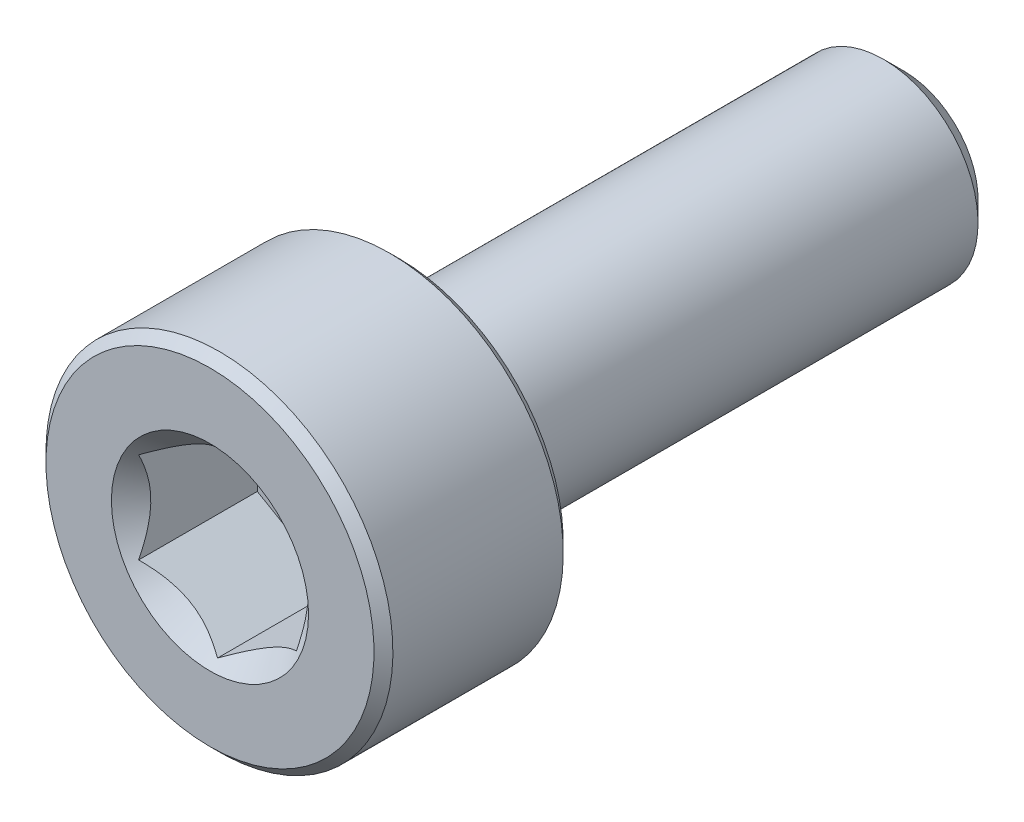
SolidWorks part; units mm, degrees
ref_plane "Front Plane" through (0, 0, 0) normal (0, 0, 1) x (1, 0, 0)
ref_plane "Top Plane" through (0, 0, 0) normal (0, 1, 0) x (1, 0, 0)
ref_plane "Right Plane" through (0, 0, 0) normal (1, 0, 0) x (0, 0, -1)
sketch "Sketch1" plane through (0, 0, 0) normal (1, 0, 0) x (0, 0, -1)
  line L0 (-5.5, 0) -> (5.5, 0) construction
  line L1 (5.5, 0) -> (5.5, 1.1752) construction
  line L2 (5.5, 1.1752) -> (5.1752, 1.5) construction
  line L3 (5.1752, 1.5) -> (5.125, 1.5) construction
  line L4 (5.125, 1.5) -> (-2.5, 1.5) construction
  line L5 (-2.5, 1.5) -> (-2.5, 2.75) construction
  line L6 (-2.5, 2.75) -> (-5.5, 2.75) construction
  line L7 (-5.5, 2.75) -> (-5.5, 0) construction
  line L8 (5.5, 1.1752) -> (5.5, 1.5) construction
  line L9 (5.4688, 1.5541) -> (5.7188, 1.1211) construction
  line L10 (5.7188, 1.1211) -> (5.9688, 1.5541) construction
  line L11 (5.9688, 1.5541) -> (5.4688, 1.5541) construction
  line L12 (5.7188, 1.5541) -> (5.7188, 1.5) construction
  line L13 (5.7188, 1.1211) -> (5.7188, 1.1752) construction
  line L14 (5.6875, 1.1752) -> (5.75, 1.1752) construction
  line L15 (5.5, 1.5) -> (5.9375, 1.5) construction
  line L16 (5.4844, 1.5271) -> (5.9531, 1.5271) construction
  line L17 (5.5, 0) -> (5.5, -1.5) construction
  line L18 (-2.65, 2.75) -> (-2.5, 2.6) construction
  line L19 (-5.35, 2.75) -> (-5.5, 2.6) construction
  line L20 (-2.5, 1.5) -> (-2.5, 0) construction
  line L21 (-2.5, 0.75) -> (0.1667, 0.75) construction
  line L22 (0.1667, 0.75) -> (2.8333, 0.75) construction
  line L23 (2.8333, 0.75) -> (5.5, 0.75) construction
  line L24 (0.1667, 0.75) -> (0.1667, 1.5) construction
  line L25 (0.1667, 1.5) -> (0.1667, 2.75) construction
  line L26 (2.8333, 0.75) -> (2.8333, 2.75) construction
  point P0 (-5.5, 1.25)
  point P3 (4.25, 1.5)
  point P4 (0, 0)
  point P18 (2.8333, 1.5)
  point P22 (5.7188, 1.1752)
  point P24 (5.125, 1.5)
  point P25 (5.7188, 1.5)
  point P28 (5.7188, 1.5271)
  point P29 (4.25, -1.5)
  point P30 (0.1667, 1.5)
  point P31 (-4, 2.75)
  point P37 (-3.025, 2.75)
  point P38 (-5.275, 2.75)
  point P45 (0.1667, 0.75)
  point P46 (2.8333, 0.75)
  dimension "D2" = 0.0625
  dimension "D7" = 0.15
  dimension "D8" = 0.15
  dimension "D9" = 0.15
  dimension "D10" = 0.075
  dimension "D11" = 0.375
  dimension "Drive Size" = 2.5
  dimension "Head Diameter" = 5.5
  dimension "Head Height" = 3
  dimension "Thread Pitch" = 0.5
  dimension "Thread Size" = 3
  dimension "Length" = 8
  dimension "D12" = 0.375
  dimension "D4" = 1.25
  dimension "D3" = 45
sketch "Sketch2" plane through (0, 0, 0) normal (1, 0, 0) x (0, 0, -1)
  line L0 (-5.5, 0) -> (-5.5, 2.6)
  line L1 (-5.35, 2.75) -> (-2.65, 2.75)
  line L2 (-2.5, 2.6) -> (-2.5, 1.65)
  line L4 (5.1752, 1.5) -> (5.5, 1.1752)
  line L5 (5.5, 1.1752) -> (5.5, 0)
  line L6 (-2.5, 2.75) -> (-5.5, 2.75) construction
  line L7 (5.5, 0) -> (-5.5, 0)
  line L8 (-5.35, 2.75) -> (-5.5, 2.6) construction
  line L10 (-5.35, 2.75) -> (-5.5, 2.6)
  line L14 (-2.65, 2.75) -> (-2.5, 2.6) construction
  line L16 (-2.65, 2.75) -> (-2.5, 2.6)
  line L17 (-2.5, 1.5) -> (-2.5, 2.75) construction
  line L19 (-2.35, 1.5) -> (5.1752, 1.5)
  line L20 (5.125, 1.5) -> (-2.5, 1.5) construction
  arc A1 (-2.5, 1.65) -> (-2.35, 1.5) centre (-2.35, 1.65) ccw
  dimension "D3" = 0.15
revolve "Revolve1" add sketch "Sketch2" angle 360 about L7
sketch "Sketch3" plane through (0, 0, 5.5) normal (0, 0, 1) x (1, 0, 0)
  line L1 (1.25, -0.7217) -> (1.25, 0.7217)
  line L2 (1.25, 0.7217) -> (0, 1.4434)
  line L3 (0, 1.4434) -> (-1.25, 0.7217)
  line L4 (-1.25, 0.7217) -> (-1.25, -0.7217)
  line L5 (-1.25, -0.7217) -> (0, -1.4434)
  line L6 (0, -1.4434) -> (1.25, -0.7217)
  circle A0 centre (0, 0) radius 1.25 construction
  circle A1 centre (0, 0) radius 2.75 construction
  circle A2 centre (0, 0) radius 2.75 construction
  circle A3 centre (0, 0) radius 1.4434 construction
  point P13 (0, 0)
extrude "Cut-Extrude1" cut sketch "Sketch3" against normal offset from surface (2 mm away) 1 up to face at (0, 2.6, 2.5)
sketch "Sketch4" plane through (0, 0, 5.5) normal (0, 0, 1) x (1, 0, 0)
  circle A0 centre (0, 0) radius 1.5625
  dimension "D1" = 3.125
extrude "Cut-Extrude2" cut sketch "Sketch4" against normal up to vertex (1.5 mm away) draft 45 up to point (0, 2.75, 4)
sketch "Sketch11" plane through (0, 0, 0) normal (1, 0, 0) x (0, 0, -1)
  line L0 (-5.5, 0) -> (5.5, 0) construction
  line L1 (-5.5, 0) -> (5.5, 0) construction
  line L2 (-1, 0) -> (-1, 1.5) construction
  line L3 (5.125, 1.5) -> (-2.5, 1.5) construction
  line L4 (4, 0) -> (4, 1.5) construction
  line L6 (5.5, 1.1752) -> (5.5, 1.5) construction
  point P2 (-1, 0)
  point P3 (4, 0)
  dimension "D1" = 1.5
  dimension "D2" = 1.5
sketch "Sketch6" [suppressed] plane through (0, 0, -5.5) normal (0, 0, -1) x (-1, 0, 0)
  circle A0 centre (0, 0) radius 1.5
curve "Helix/Spiral1" [suppressed] pitch 0.5 height 8.5 turns 17
sketch "Sketch10" [suppressed] plane through (0, 0, 0) normal (1, 0, 0) x (0, 0, -1)
  line L0 (-2.35, -2.75) -> (-2.35, 2.75)
  line L5 (-5.5, 0) -> (5.5, 0) construction
  line L6 (-2.35, 1.5) -> (-2.35, -1.5) construction
  point P3 (-2.35, 0)
split "Split1" [suppressed] bodies to split 106
sketch "Sketch7" [suppressed] plane through (0, 0, 0) normal (1, 0, 0) x (0, 0, -1)
  line L0 (5.4844, 1.5271) -> (5.9531, 1.5271)
  line L1 (5.9531, 1.5271) -> (5.75, 1.1752)
  line L2 (5.75, 1.1752) -> (5.6875, 1.1752)
  line L3 (5.6875, 1.1752) -> (5.4844, 1.5271)
sweep "Cut-Sweep1" [suppressed] cut profiles "Sketch7" path "Helix/Spiral1"
sketch "Sketch8" [suppressed] plane through (0, 0, 0) normal (1, 0, 0) x (0, 0, -1)
  line L0 (-2.5, 0) -> (-2.5, 1.5)
  line L1 (-2.35, -1.5) -> (-2.35, 1.5) construction
  line L2 (-2.5, 1.5) -> (-2.35, 1.5)
  line L4 (-2.35, 1.5) -> (-1.484, 0)
  line L5 (-1.484, 0) -> (-2.5, 0)
  line L6 (5.125, 1.5) -> (-2.5, 1.5) construction
  line L7 (-5.5, 0) -> (5.5, 0) construction
  dimension "D1" = 60
revolve "Revolve2" [suppressed] add sketch "Sketch8" angle 360 about L5
ref_plane "Plane1" [suppressed] through (0, 0, 5.5) normal (0, 0, 1) x (1, 0, 0)
sketch "Sketch12" [suppressed] plane through (0, 0, 5.5) normal (0, 0, 1) x (1, 0, 0)
  line L0 (0, 0) -> (0.096, 2.7483) construction
  line L1 (0, 0) -> (-0.096, 2.7483) construction
  line L2 (0, 2.6812) -> (0, 2.8187) construction
  line L3 (-0.1664, 2.8187) -> (0.1664, 2.8187)
  line L4 (-0.1664, 2.8187) -> (-0.0493, 2.7017)
  line L5 (0.0493, 2.7017) -> (0.1664, 2.8187)
  circle A0 centre (0, 0) radius 2.75 construction
  arc A1 (-0.0493, 2.7017) -> (0.0493, 2.7017) centre (0, 2.751) ccw
  point P9 (0, 2.8187)
  point P13 (0, 2.75)
  dimension "D1" = 4
  dimension "D2" = 0.0688
extrude "Cut-Extrude3" [suppressed] cut sketch "Sketch12" against normal blind 2.4
pattern_circular "CirPattern1" [suppressed] count 72 over 360 about axis through (0, 0, 5.5) along (0, 0, -1) of bodies 118
equation "\"D2@Sketch1\" = \"Thread Pitch@Sketch1\" / 8"
equation "\"D4@Helix/Spiral1\" = \"Thread Pitch@Sketch1\""
equation "\"D7@Sketch1\" = \"Head Height@Sketch1\" * .05"
equation "\"D8@Sketch1\"=\"D7@Sketch1\""
equation "\"D9@Sketch1\"=\"D7@Sketch1\""
equation "\"D10@Sketch1\"=\"D7@Sketch1\"/2"
equation "\"D11@Sketch1\"=\"D10@Sketch1\"*5"
equation "\"D4@Sketch1\"=\"Thread Pitch@Sketch1\"*2.5"
equation "\"D12@Sketch1\"=\"Thread Pitch@Sketch1\"*.75"
equation "\"D3@Helix/Spiral1\"=\"Length@Sketch1\"+\"Thread Pitch@Sketch1\""
equation "\"D3@Sketch2\" = \"Thread Size@Sketch1\" * 0.05"
equation "\"D1@Sketch11\"=\"Length@Sketch1\"*0.1875"
equation "\"D2@Sketch11\"=\"D1@Sketch11\""
equation "\"D2@Sketch12\"=\"Head Diameter@Sketch1\"*.0125"
equation "\"D1@Cut-Extrude3\"=\"Head Height@Sketch1\"*.8"
equation "\"D1@CirPattern1\"=\"D3@CirPattern1\"/(1.25*\"D1@Sketch12\")"
equation "\"D1@Sketch4\"=\"Drive Size@Sketch1\"*1.25"
